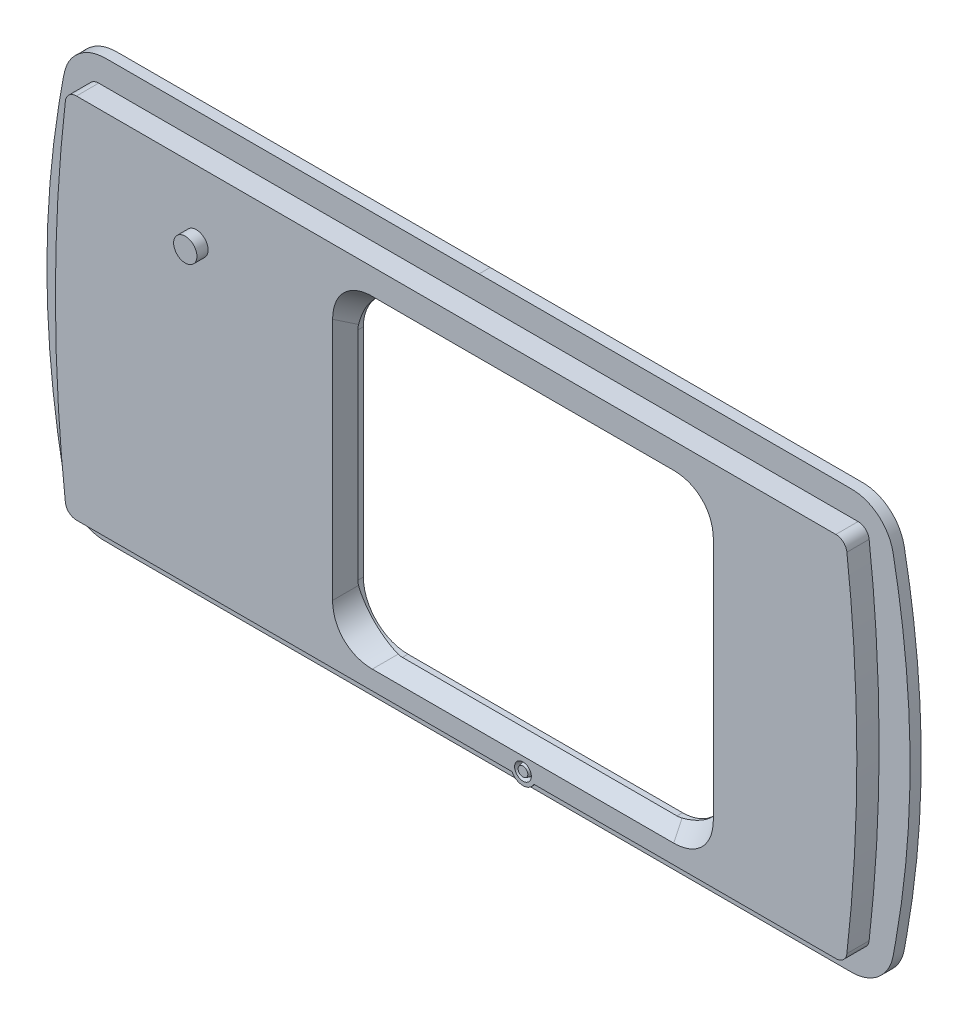
SolidWorks part; units mm, degrees
ref_plane "前视基准面" through (0, 0, 0) normal (0, 0, 1) x (1, 0, 0)
ref_plane "上视基准面" through (0, 0, 0) normal (0, 1, 0) x (1, 0, 0)
ref_plane "右视基准面" through (0, 0, 0) normal (1, 0, 0) x (0, 0, -1)
ref_plane "基准面1" through (0, 0, 2) normal (0, 0, 1) x (1, 0, 0)
sketch "草图2" plane through (0, 0, 2) normal (0, 0, 1) x (1, 0, 0)
  line L0 (54.5158, -0.6869) -> (47.0272, -0.6869) construction
  line L1 (35.0407, -17.1869) -> (-34.9593, -17.1869)
  line L3 (35.0407, 15.8131) -> (-34.9593, 15.8131)
  line L5 (35.0407, -17.1869) -> (37.0407, -0.6869) construction
  line L6 (0.0407, -14.3684) -> (0.0407, -18.5079) construction
  line L7 (37.0407, -0.6869) -> (35.0407, 15.8131) construction
  line L16 (-34.9593, -17.1869) -> (-36.9593, -0.6869) construction
  line L17 (-36.9593, -0.6869) -> (-34.9593, 15.8131) construction
  line L18 (0.0407, -33.1433) -> (0.0407, -27.2901) construction
  spline S2 degree 2 poles (35.0407, -17.1869) (37.0407, -0.6869) (35.0407, 15.8131) knots 0 0 0 1 1 1
  spline S8 degree 2 poles (-34.9593, -17.1869) (-36.9593, -0.6869) (-34.9593, 15.8131) knots 0 0 0 1 1 1
  point P9 (0.0407, -17.1869)
  dimension "D1" = 70
  dimension "D2" = 33
  dimension "D3" = 16.5
  dimension "D4" = 37
  dimension "D5" = 37
extrude "凸台-拉伸1" add sketch "草图2" against normal blind 2
fillet "圆角1" radius 1 4 edges at (35.0407, -17.1869, 1) (35.0407, 15.8131, 1) (-34.9593, 15.8131, 1) (-34.9593, -17.1869, 1)
sketch "草图6" plane through (0, 0, 2) normal (0, 0, 1) x (1, 0, 0)
  line L1 (-11.0554, -15.4869) -> (23.1446, -15.4869)
  line L2 (-11.0554, -15.4869) -> (-11.0554, 13.5131)
  line L3 (-11.0554, 13.5131) -> (23.1446, 13.5131)
  line L4 (23.1446, -15.4869) -> (23.1446, 13.5131)
  line L6 (-34.0703, -17.1869) -> (34.1518, -17.1869) construction
  dimension "D3" = 34.2
  dimension "D4" = 29
  dimension "D5" = 1.7
extrude "切除-拉伸1" cut sketch "草图6" against normal blind 1.5 draft 27
sketch "草图7" plane through (0, 0, 0.5) normal (0, 0, 1) x (1, 0, 0)
  line L5 (-10.2911, -14.7226) -> (22.3803, -14.7226)
  line L7 (22.3803, 12.7488) -> (-10.2911, 12.7488)
  line L9 (-10.2911, -14.7226) -> (22.3803, -14.7226)
  line L11 (22.3803, 12.7488) -> (-10.2911, 12.7488)
  line L12 (-10.2911, 12.7488) -> (-10.2911, -14.7226)
  line L14 (22.3803, -14.7226) -> (22.3803, 12.7488)
  line L15 (22.3803, -14.7226) -> (22.3803, 12.7488)
  line L16 (-10.2911, 12.7488) -> (-10.2911, -14.7226)
  dimension "D1" = 0
extrude "切除-拉伸2" cut sketch "草图7" against normal blind 1
fillet "圆角2" radius 4 8 edges at (-10.2911, 12.7488, 0.25) (-10.6733, 13.131, 1.25) (22.3803, 12.7488, 0.25) (22.7624, 13.131, 1.25) (-10.6733, -15.1047, 1.25) (-10.2911, -14.7226, 0.25) (22.7624, -15.1047, 1.25) (22.3803, -14.7226, 0.25)
sketch "草图8" plane through (0, 0, 0) normal (0, 0, -1) x (-1, 0, 0)
  line L0 (-0.0407, -41.6024) -> (-0.0407, -23.5952) construction
  line L1 (33.9593, -16.1869) -> (-34.0407, -16.1869)
  line L2 (33.9593, -16.1869) -> (33.9593, 14.8131)
  line L3 (33.9593, 14.8131) -> (-34.0407, 14.8131)
  line L4 (-34.0407, -16.1869) -> (-34.0407, 14.8131)
  line L5 (34.0703, -17.1869) -> (-34.1518, -17.1869) construction
  line L6 (-0.0407, 17.4782) -> (-0.0407, 17.2771) construction
  spline S2 degree 3 poles (-0.1, 18.0561) (-2.385, 18.0561) (-6.955, 18.0561) (-12.6676, 18.0561) (-17.2376, 18.0561) (-20.6651, 18.0562) (-24.0926, 18.056) (-26.9489, 18.0567) (-29.2338, 18.0552) (-30.9477, 18.0596) (-32.661, 18.0433) (-34.3767, 18.1042) (-35.9339, 17.377) (-36.8537, 16.291) (-37.2574, 15.2445) (-37.4407, 14.1272) (-37.7009, 12.7286) (-37.9587, 11.043) (-38.2656, 8.7917) (-38.5605, 5.9749) (-38.7756, 2.5883) (-38.8482, -0.8045) (-38.7752, -4.2032) (-38.5562, -7.6102) (-38.2527, -10.4329) (-37.9396, -12.6842) (-37.675, -14.3674) (-37.4171, -15.771) (-37.2199, -16.8792) (-36.767, -17.9079) (-35.8108, -18.9543) (-34.4863, -19.5147) (-33.372, -19.5493) (-32.2285, -19.5407) (-30.8098, -19.5449) (-29.1028, -19.5436) (-26.8283, -19.544) (-23.9848, -19.5438) (-20.5727, -19.5439) (-17.1606, -19.5439) (-10.3363, -19.5439) (-4.6495, -19.5439) (-0.1, -19.5439) knots 0.00091 0.00091 0.00091 0.00091 0.063296 0.125682 0.156875 0.188068 0.219261 0.250454 0.266051 0.281647 0.297243 0.31284 0.328436 0.344033 0.351831 0.359629 0.375226 0.390822 0.406419 0.437612 0.468805 0.499998 0.531191 0.562384 0.593577 0.609173 0.62477 0.640366 0.648165 0.655963 0.671559 0.687156 0.694954 0.702752 0.718349 0.733945 0.749542 0.780735 0.811928 0.843121 0.874314 0.999086 0.999086 0.999086 0.999086
  spline S3 degree 3 poles (-0.1, -19.5439) (4.4577, -19.5439) (10.1548, -19.5439) (16.9914, -19.5439) (20.4097, -19.5439) (23.8279, -19.5438) (26.6766, -19.544) (28.9551, -19.5437) (30.6652, -19.5446) (32.0867, -19.5417) (33.2317, -19.5476) (34.3482, -19.5237) (35.6747, -18.9789) (36.6409, -17.9446) (37.1066, -16.9243) (37.3103, -15.8215) (37.5649, -14.4218) (37.831, -12.7433) (38.1447, -10.498) (38.4489, -7.69) (38.6702, -4.3134) (38.748, -0.9307) (38.681, 2.4573) (38.4708, 5.8546) (38.1793, 8.6717) (37.8776, 10.9173) (37.6198, 12.5981) (37.3229, 14.2733) (37.0182, 15.9459) (35.934, 17.2946) (34.4061, 18.0807) (32.6795, 18.0496) (30.9546, 18.0579) (29.2293, 18.0557) (26.929, 18.0564) (24.0535, 18.056) (20.603, 18.0562) (17.1525, 18.0561) (12.5519, 18.0561) (6.801, 18.0561) (2.2003, 18.0561) (-0.1, 18.0561) knots 0 0 0 0 0.125 0.15625 0.1875 0.21875 0.25 0.265625 0.28125 0.296875 0.304688 0.3125 0.328125 0.34375 0.351562 0.359375 0.375 0.390625 0.40625 0.4375 0.46875 0.5 0.53125 0.5625 0.59375 0.609375 0.625 0.640625 0.65625 0.671875 0.6875 0.703125 0.71875 0.734375 0.75 0.78125 0.8125 0.84375 0.875 0.9375 1 1 1 1
  point P5 (-0.0407, -16.1869)
  dimension "D1" = 68
  dimension "D2" = 31
  dimension "D3" = 1
extrude "凸台-拉伸5" add sketch "草图8" along normal blind 1
sketch "草图9" plane through (0, 0, 2) normal (0, 0, 1) x (1, 0, 0)
  line L0 (-7.4914, -15.4869) -> (19.5806, -15.4869) construction
  circle A0 centre (6.0446, -16.6869) radius 1.1
  point P5 (6.0446, -15.4869)
  dimension "D2" = 2.2
  dimension "D1" = 1.2
extrude "凸台-拉伸6" add sketch "草图9" against normal blind 2
sketch "草图10" plane through (0, 0, 2) normal (0, 0, 1) x (1, 0, 0)
  circle A0 centre (6.0446, -16.6869) radius 0.75
  dimension "D1" = 1.5
extrude "切除-拉伸3" cut sketch "草图10" against normal blind 0.5 draft 20
sketch "草图11" plane through (0, 0, 1.5) normal (0, 0, 1) x (1, 0, 0)
  circle A0 centre (6.0446, -16.6869) radius 0.568 construction
  circle A1 centre (6.0446, -16.6869) radius 0.568
extrude "凸台-拉伸7" add sketch "草图11" along normal blind 0.5 draft 15
sketch "草图12" plane through (0, 0, 2) normal (0, 0, 1) x (1, 0, 0)
  line L0 (-10.2911, 8.7488) -> (-10.2911, -10.7226) construction
  line L1 (18.3803, 12.7488) -> (-6.2911, 12.7488) construction
  circle A0 centre (-23.2911, 9.7488) radius 1.0466
  dimension "D1" = 13
  dimension "D2" = 3
extrude "凸台-拉伸8" add sketch "草图12" along normal blind 1
